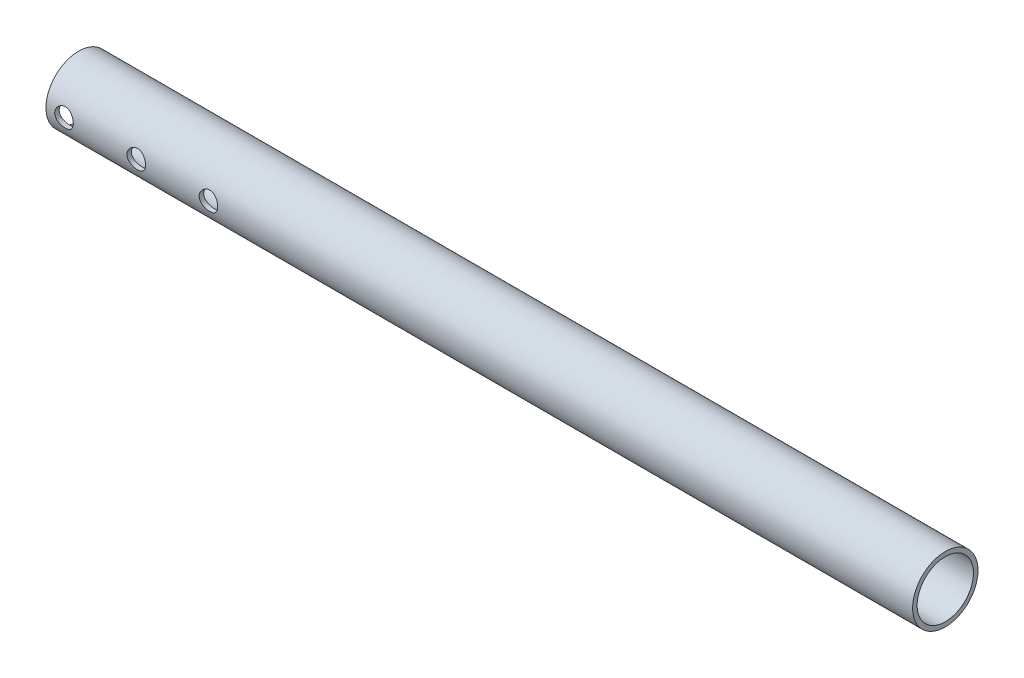
SolidWorks part; units mm, degrees
ref_plane "Front Plane" through (0, 0, 0) normal (0, 0, 1) x (1, 0, 0)
ref_plane "Top Plane" through (0, 0, 0) normal (0, 1, 0) x (1, 0, 0)
ref_plane "Right Plane" through (0, 0, 0) normal (1, 0, 0) x (0, 0, -1)
sketch "Sketch1" plane through (0, 0, 0) normal (1, 0, 0) x (0, 0, -1)
  circle A0 centre (0, 0) radius 11.5
  circle A1 centre (0, 0) radius 9.9125
  dimension "D1" = 1.5875
extrude "Boss-Extrude1" add sketch "Sketch1" along normal blind 304.8
ref_plane "Plane1" through (0, 0, 10) normal (0, 0, 1) x (1, 0, 0)
sketch "Sketch2" plane through (0, 0, 10) normal (0, 0, 1) x (1, 0, 0)
  line L0 (0, 0) -> (304.8, 0) construction
  line L1 (304.8, -11.5) -> (304.8, 11.5) construction
  circle A0 centre (6.35, 0) radius 3.2639
  circle A1 centre (31.75, 0) radius 3.2639
  circle A2 centre (57.15, 0) radius 3.2639
  dimension "D1" = 6.35
  dimension "D2" = 3
extrude "Cut-Extrude1" cut sketch "Sketch2" against normal through all and the other way through all
equation "\"1f\"=10"
